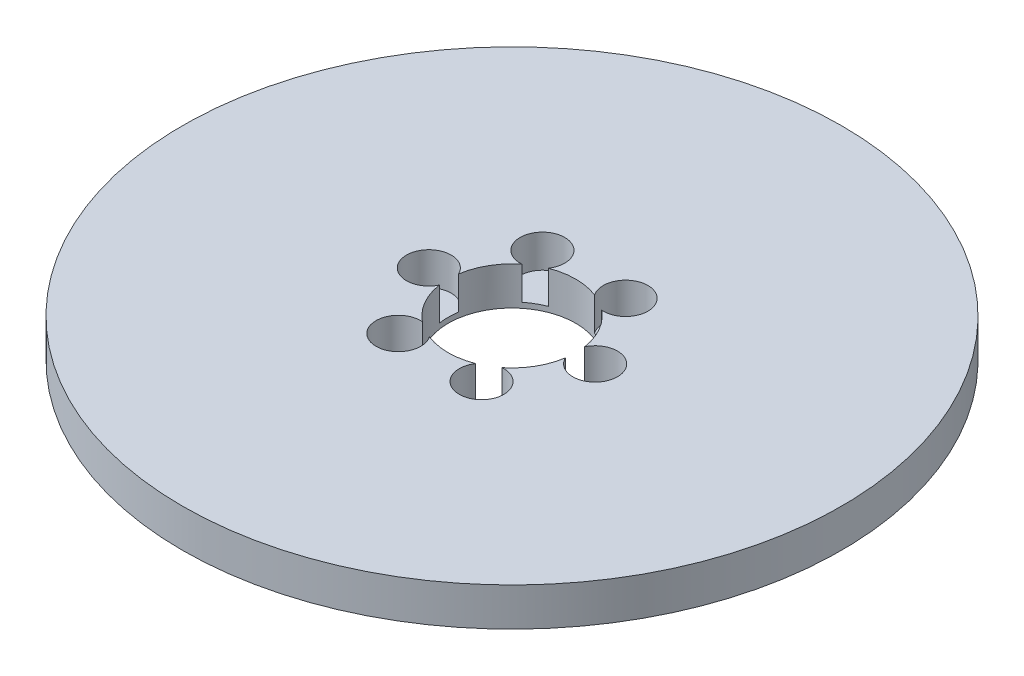
SolidWorks part; units mm, degrees
ref_plane "Front Plane" through (0, 0, 0) normal (0, 0, 1) x (1, 0, 0)
ref_plane "Top Plane" through (0, 0, 0) normal (0, 1, 0) x (1, 0, 0)
ref_plane "Right Plane" through (0, 0, 0) normal (1, 0, 0) x (0, 0, -1)
sketch "Sketch1" plane through (0, 0, 0) normal (0, 1, 0) x (1, 0, 0)
  circle A0 centre (0, 0) radius 77.5
  dimension "FLANGE_OD" = 155
extrude "Boss-Extrude1" add sketch "Sketch1" along normal blind 9
sketch "Sketch2" plane through (0, 0, 0) normal (0, 1, 0) x (1, 0, 0)
  circle A0 centre (0, 0) radius 15
  dimension "BORE_D" = 30
extrude "Cut-Extrude1" cut sketch "Sketch2" along normal through all
sketch "Sketch3" plane through (0, 9, 0) normal (0, 1, 0) x (1, 0, 0)
  circle A0 centre (0, 0) radius 19.5581 construction
  circle A1 centre (-19.5581, 0) radius 5.2477
  dimension "BOLT_D" = 10.4954
  dimension "BOLT_PCD" = 39.1162
extrude "Cut-Extrude2" cut sketch "Sketch3" against normal blind 7.7599
pattern_circular "CirPattern1" count 6 over 360 about axis through (0, 0, 0) along (0, 1, 0) of "Cut-Extrude2"
